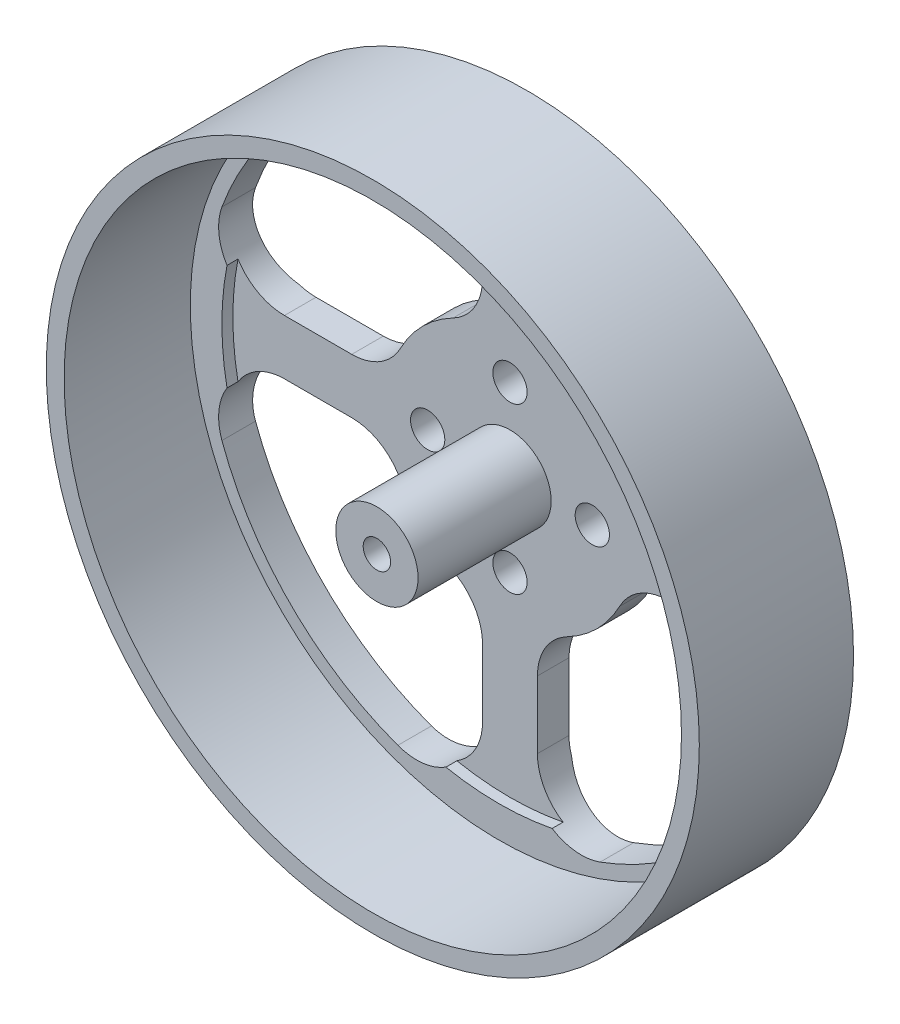
SolidWorks part; units mm, degrees
material "Plain Carbon Steel"
ref_plane "Front Plane" through (0, 0, 0) normal (0, 0, 1) x (1, 0, 0)
ref_plane "Top Plane" through (0, 0, 0) normal (0, 1, 0) x (1, 0, 0)
ref_plane "Right Plane" through (0, 0, 0) normal (1, 0, 0) x (0, 0, -1)
sketch "Sketch1" plane through (0, 0, 0) normal (0, 0, 1) x (1, 0, 0)
  circle A0 centre (0, 0) radius 23.8
  dimension "D2" = 47.6
extrude "Boss-Extrude1" add sketch "Sketch1" along normal blind 2.3
sketch "Sketch2" plane through (0, 0, 2.3) normal (0, 0, 1) x (1, 0, 0)
  circle A0 centre (0, 0) radius 23.8
  circle A1 centre (0, 0) radius 20.2
  dimension "D1" = 40.4
extrude "Boss-Extrude2" add sketch "Sketch2" along normal blind 10
sketch "Sketch3" plane through (0, 0, 2.3) normal (0, 0, 1) x (1, 0, 0)
  circle A0 centre (0, 0) radius 3
extrude "Boss-Extrude3" add sketch "Sketch3" along normal blind 9.7
chamfer "Chamfer1" distance 6 angle 10 1 edges at (23.8, 0, 0) first distance on face at (23.8, 0, 0)
sketch "Sketch4" plane through (0, 0, 0) normal (0, 0, -1) x (-1, 0, 0)
  circle A0 centre (0, 0) radius 6 construction
  circle A1 centre (6, 0) radius 1.25
  circle A2 centre (0, -6) radius 1.25
  circle A3 centre (-6, 0) radius 1.25
  circle A4 centre (0, 6) radius 1.25
  point P14 (0, 0)
  dimension "D1" = 12
  dimension "D2" = 4
  dimension "D3" = 2.5
extrude "Cut-Extrude1" cut sketch "Sketch4" against normal blind 15
sketch "Sketch5" plane through (0, 0, 0) normal (0, 0, 1) x (1, 0, 0)
  line L0 (0, 9) -> (0, 21.5) construction
  line L1 (2, 21.4068) -> (2, 8.775)
  line L2 (-2, 21.4068) -> (-2, 8.775)
  line L3 (21.4068, -2) -> (8.775, -2)
  line L4 (21.4068, 2) -> (8.775, 2)
  line L5 (-2, -21.4068) -> (-2, -8.775)
  line L6 (2, -21.4068) -> (2, -8.775)
  line L7 (-21.4068, 2) -> (-8.775, 2)
  line L8 (-21.4068, -2) -> (-8.775, -2)
  circle A0 centre (0, 0) radius 21.5
  circle A1 centre (0, 0) radius 9
  point P25 (0.6367, 0.7197)
  point P26 (-0.147, -0.01)
  point P27 (-0.2, 0)
  point P28 (0, 0)
  dimension "D1" = 2
  dimension "D2" = 43
  dimension "D3" = 18
  dimension "D4" = 4
extrude "Cut-Extrude2" cut sketch "Sketch5" along normal through all
fillet "Fillet1" radius 4 16 edges at (-21.4068, -2, 6.4762) (-21.4068, 2, 6.4762) (2, -21.4068, 6.4762) (-2, -21.4068, 6.4762) (-8.775, 2, 1.15) (-2, 8.775, 1.15) (2, 8.775, 1.15) (8.775, 2, 1.15) (-8.775, -2, 1.15) (-2, -8.775, 1.15) (2, -8.775, 1.15) (8.775, -2, 1.15) (21.4068, -2, 6.4762) (21.4068, 2, 6.4762) (2, 21.4068, 6.4762) (-2, 21.4068, 6.4762)
sketch "Sketch6" plane through (0, 0, 12.3) normal (0, 0, 1) x (1, 0, 0)
  circle A0 centre (0, 0) radius 22.5
  circle A1 centre (0, 0) radius 20.2
extrude "Cut-Extrude3" cut sketch "Sketch6" against normal blind 9.2
sketch "Sketch7" plane through (0, 0, 12) normal (0, 0, 1) x (1, 0, 0)
  circle A0 centre (0, 0) radius 1
  dimension "D1" = 2
extrude "Cut-Extrude4" cut sketch "Sketch7" against normal blind 5
